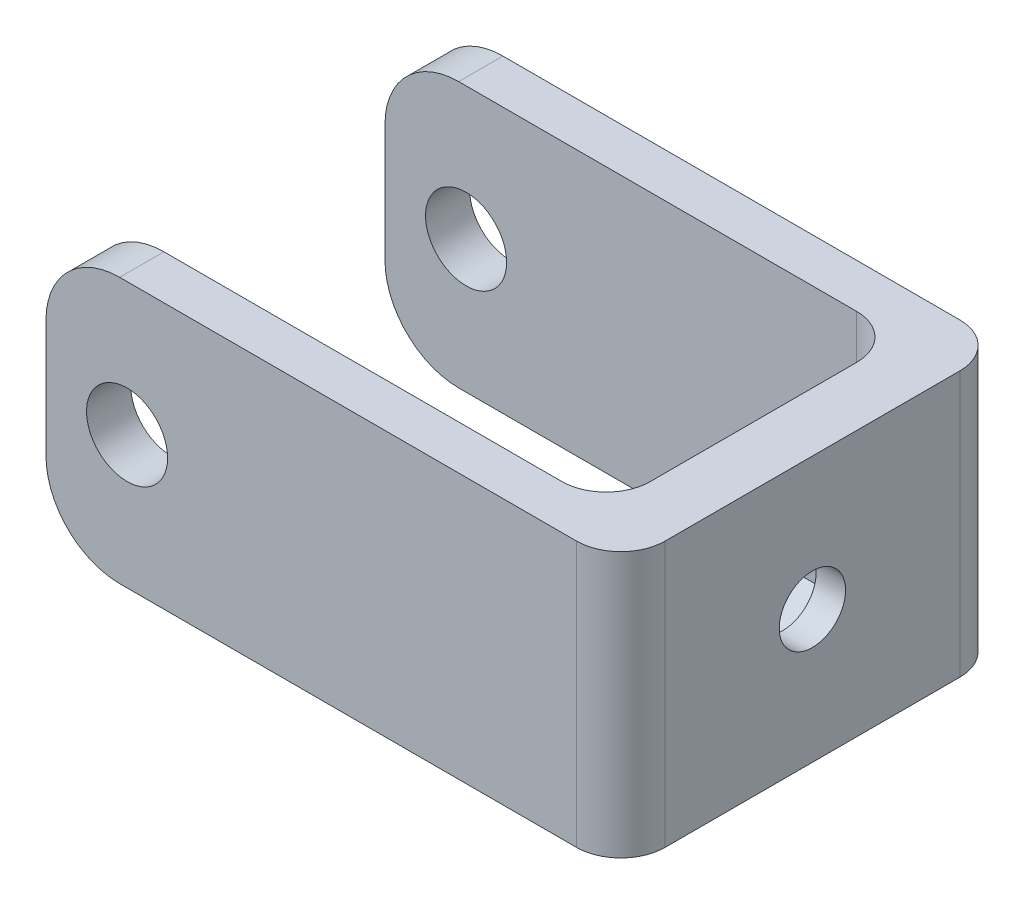
SolidWorks part; units mm, degrees
ref_plane "Front Plane" through (0, 0, 0) normal (0, 0, 1) x (1, 0, 0)
ref_plane "Top Plane" through (0, 0, 0) normal (0, 1, 0) x (1, 0, 0)
ref_plane "Right Plane" through (0, 0, 0) normal (1, 0, 0) x (0, 0, -1)
sketch "Sketch1" plane through (0, 0, 0) normal (1, 0, 0) x (0, 0, -1)
  line L1 (-13, -9) -> (13, -9)
  line L2 (-13, -9) -> (-13, 9)
  line L3 (-13, 9) -> (13, 9)
  line L4 (13, -9) -> (13, 9)
  line L5 (-13, -9) -> (13, 9) construction
  line L6 (-13, 9) -> (13, -9) construction
  point P0 (0, 0)
  dimension "D1" = 18
  dimension "D2" = 26
extrude "Boss-Extrude1" add sketch "Sketch1" along normal blind 4
sketch "Sketch2" plane through (0, 0, 0) normal (-1, 0, 0) x (0, 0, 1)
  line L0 (13, -9) -> (-13, -9) construction
  line L1 (-13, 9) -> (-10, 9)
  line L2 (-13, 9) -> (-13, -9)
  line L3 (-13, -9) -> (-10, -9)
  line L4 (-10, 9) -> (-10, -9)
  line L6 (13, 9) -> (10, 9)
  line L7 (13, 9) -> (13, -9)
  line L8 (13, -9) -> (10, -9)
  line L9 (10, 9) -> (10, -9)
  dimension "D1" = 3
  dimension "D2" = 3
extrude "Boss-Extrude2" add sketch "Sketch2" along normal blind 35
sketch "Sketch3" plane through (0, 0, 13) normal (0, 0, 1) x (1, 0, 0)
  line L1 (-35, -9) -> (-35, 9) construction
  circle A0 centre (-29.5, 0) radius 2.75
  dimension "D1" = 5.5
  dimension "D2" = 5.5
extrude "Cut-Extrude1" cut sketch "Sketch3" against normal through all
fillet "Fillet1" radius 3 4 edges at (0, 0, 10) (4, 0, 13) (4, 0, -13) (0, 0, -10)
fillet "Fillet2" radius 5 4 edges at (-35, 9, -11.5) (-35, -9, -11.5) (-35, -9, 11.5) (-35, 9, 11.5)
sketch "Sketch5" plane through (0, 0, 0) normal (-1, 0, 0) x (0, 0, 1)
  circle A0 centre (0, 0) radius 7
  dimension "D1" = 14
extrude "Boss-Extrude3" add sketch "Sketch5" along normal blind 2
sketch "Sketch7" plane through (4, 0, 0) normal (1, 0, 0) x (0, 0, -1)
  circle A0 centre (0, 0) radius 2.25
  dimension "D1" = 4.5
extrude "Cut-Extrude3" cut sketch "Sketch7" against normal up to next
sketch "Sketch8" plane through (-2, 0, 0) normal (-1, 0, 0) x (0, 0, 1)
  line L1 (0, 4.3301) -> (-3.75, 2.1651)
  line L2 (-3.75, 2.1651) -> (-3.75, -2.1651)
  line L3 (-3.75, -2.1651) -> (0, -4.3301)
  line L4 (0, -4.3301) -> (3.75, -2.1651)
  line L5 (3.75, -2.1651) -> (3.75, 2.1651)
  line L6 (3.75, 2.1651) -> (0, 4.3301)
  circle A0 centre (0, 0) radius 3.75 construction
  dimension "D1" = 7.5
extrude "Cut-Extrude4" cut sketch "Sketch8" against normal blind 4
chamfer "Chamfer1" distance 2 angle 45 2 edges at (0, 7, 0) (0, -7, 0)
